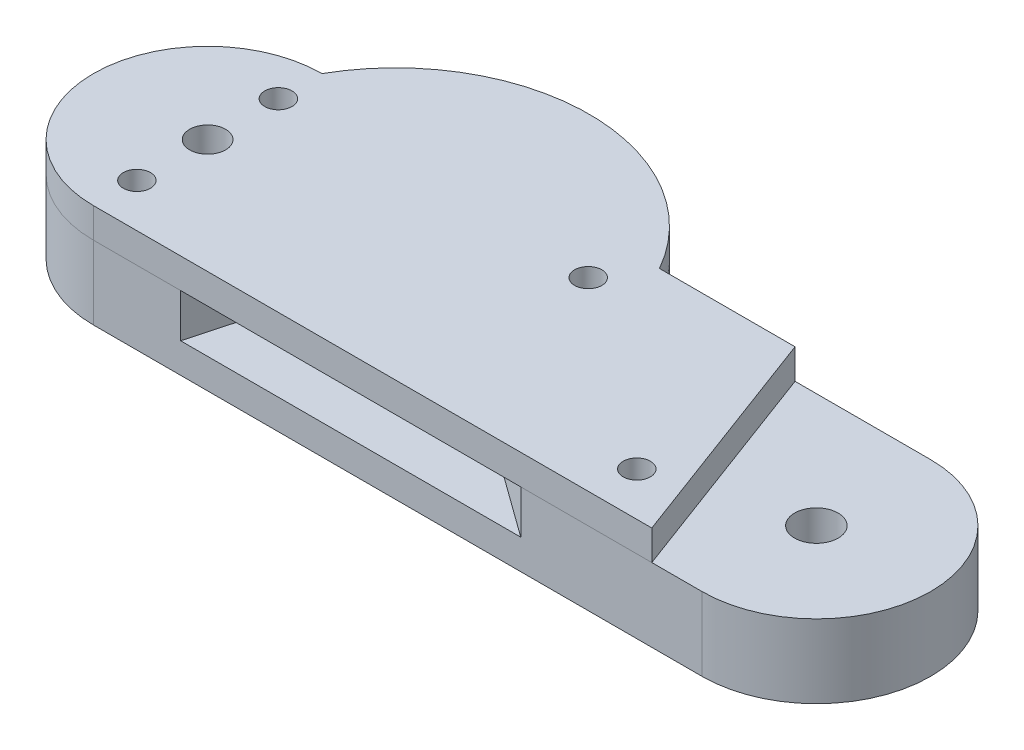
SolidWorks part; units mm, degrees
ref_plane "Front Plane" through (0, 0, 0) normal (0, 0, 1) x (1, 0, 0)
ref_plane "Top Plane" through (0, 0, 0) normal (0, 1, 0) x (1, 0, 0)
ref_plane "Right Plane" through (0, 0, 0) normal (1, 0, 0) x (0, 0, -1)
sketch "Sketch1" plane through (0, 0, 0) normal (0, 1, 0) x (1, 0, 0)
  line L0 (0, -10.5004) -> (-55.9305, -10.5004)
  line L1 (0, 10.5004) -> (-55.9305, 10.5004)
  line L5 (0, 11.5004) -> (-55.9305, 11.5004) construction
  line L6 (0, -11.5004) -> (-55.9305, -11.5004) construction
  circle A0 centre (0, 0) radius 2
  arc A1 (0, -10.5004) -> (0, 10.5004) centre (0, 0) ccw
  arc A2 (-55.9305, 10.5004) -> (-55.9305, -10.5004) centre (-55.9305, 0) ccw
  circle A3 centre (-55.9305, 0) radius 1.65
  arc A7 (0, -11.5004) -> (0, 11.5004) centre (0, 0) ccw construction
  arc A8 (-55.9305, 11.5004) -> (-55.9305, -11.5004) centre (-55.9305, 0) ccw construction
  arc A9 (-67.2423, -5.04) -> (-54.9145, -15.6487) centre (-55.7741, -4.1805) ccw construction
  arc A10 (-55.9305, 10.5004) -> (-55.9305, -10.5004) centre (-55.9305, 0) ccw construction
  dimension "D1" = 4
  dimension "D2" = 1
  dimension "D3" = 3.3
  dimension "D4" = 55.9305
extrude "Boss-Extrude1" add sketch "Sketch1" along normal mid plane 9.5
sketch "Sketch3" plane through (0, 0, 0) normal (0, 1, 0) x (1, 0, 0)
  line L0 (0, 0) -> (-47.1525, -15.3208) construction
  line L1 (0, 0) -> (24.7895, -42.9367) construction
  line L2 (0, 0) -> (-55.9305, 0) construction
  line L3 (24.7895, -42.9367) -> (-41.5934, 5.0595) construction
  line L4 (-41.5934, 5.0595) -> (-47.1525, -15.3208) construction
  line L5 (-41.5934, 5.0595) -> (-37.6461, 19.5308) construction
  line L6 (-41.5934, 5.0595) -> (-53.749, 13.8482) construction
  line L7 (22.8477, -44.0007) -> (-38.0092, 0) construction
  line L8 (-35.7518, 18.8753) -> (-39.2995, 5.869)
  line L9 (-43.8873, 4.25) -> (-54.8123, 12.149)
  line L11 (26.6452, -41.8104) -> (-39.2995, 5.869)
  line L12 (-39.6108, 19.9279) -> (-42.7627, 8.3729) construction
  line L13 (-42.7627, 8.3729) -> (-52.4686, 15.3905) construction
  line L14 (-40.9004, 0) -> (-45.9674, -18.5763) construction
  line L15 (-43.8873, 4.25) -> (-48.2065, -11.585)
  line L18 (-40.4216, 6.6802) -> (-50.8477, 14.2185) construction
  line L20 (-41.5934, 5.0595) -> (-52.0196, 12.5978) construction
  line L21 (-42.7652, 3.4387) -> (-53.1914, 10.977) construction
  line L23 (-43.5229, 5.5858) -> (-49.082, -14.7945) construction
  line L26 (-39.6639, 4.5332) -> (-45.223, -15.8471) construction
  line L27 (25.9613, -41.316) -> (-40.4216, 6.6802) construction
  line L28 (23.6177, -44.5574) -> (-42.7652, 3.4387) construction
  arc A1 (-48.2065, -11.585) -> (26.6452, -41.8104) centre (0, 0) ccw
  arc A4 (-55.9305, 10.5004) -> (-55.9305, -10.5004) centre (-55.9305, 0) ccw construction
  arc A7 (-35.7518, 18.8753) -> (-54.8123, 12.149) centre (-41.5934, 5.0595) ccw
  dimension "D1" = 99.1581
  dimension "D3" = 120
  dimension "D6" = 30
  dimension "D2" = 18
  dimension "D4" = 2
  dimension "D5" = 2
extrude "Cut-Extrude1" cut sketch "Sketch3" against normal mid plane 4
sketch "Sketch5" plane through (0, 0, 0) normal (0, 1, 0) x (1, 0, 0)
  line L0 (-40.4241, 1.7461) -> (-52.5322, 10.5004) construction
  line L1 (-40.4241, 1.7461) -> (-35.7382, 18.9254) construction
  line L2 (-52.5322, 10.5004) -> (-43.8873, 4.25) construction
  line L3 (-39.2995, 5.869) -> (-38.0362, 10.5004) construction
  line L4 (-55.9305, 10.5004) -> (-24.9177, 10.5004)
  line L5 (0, 10.5004) -> (-55.9305, 10.5004) construction
  circle A0 centre (-40.4241, 1.7461) radius 17.807
extrude "Boss-Extrude2" add sketch "Sketch5" along normal up to surface and the other way up to surface contours A0 region at (-40.4241, 0, -14.2141) up to face at (0, 4.75, 2) other way up to face at (-27.9653, -4.75, 0)
sketch "Sketch6" plane through (0, 0, 0) normal (0, 1, 0) x (1, 0, 0)
  line L0 (-39.2995, 5.869) -> (-16.6593, -10.5004)
  line L1 (-47.9107, -10.5004) -> (-43.8873, 4.25)
  line L2 (-43.8873, 4.25) -> (-54.8544, 12.1794)
  line L3 (-39.2995, 5.869) -> (-35.7382, 18.9254)
  line L4 (-16.6593, -10.5004) -> (-39.2995, 5.869) construction
  line L5 (-43.8873, 4.25) -> (-47.9107, -10.5004) construction
  line L6 (-52.5322, 10.5004) -> (-43.8873, 4.25) construction
  line L7 (-39.2995, 5.869) -> (-38.0362, 10.5004) construction
  line L8 (-55.9305, -10.5004) -> (0, -10.5004) construction
  line L9 (-16.6593, -10.5004) -> (-47.9107, -10.5004)
  arc A0 (-24.9177, 10.5004) -> (-55.9305, 10.5004) centre (-40.4241, 1.7461) ccw construction
  arc A1 (-35.7382, 18.9254) -> (-54.8544, 12.1794) centre (-40.4241, 1.7461) ccw
extrude "Cut-Extrude2" cut sketch "Sketch6" against normal mid plane 4
sketch "Sketch7" plane through (0, -4.75, 0) normal (0, -1, 0) x (1, 0, 0)
  line L0 (0, 0) -> (4.5965, 4.5965) construction
  line L1 (0, 0) -> (6.5004, 0) construction
  line L4 (0, 6.5004) -> (-55.9305, 6.5004)
  line L5 (-27.4616, -6.5004) -> (0, -6.5004)
  line L6 (0, 6.5004) -> (-55.9305, 6.5004) construction
  line L7 (-55.9305, -6.5004) -> (0, -6.5004) construction
  circle A3 centre (-27.4616, -6.5004) radius 1.25
  circle A4 centre (0, -6.5004) radius 1.25 construction
  circle A5 centre (4.5965, 4.5965) radius 1.25 construction
  arc A6 (0, -6.5004) -> (0, 6.5004) centre (0, 0) ccw
  arc A7 (-55.9305, 6.5004) -> (-53.5442, -6.0466) centre (-55.9305, 0) ccw
  arc A8 (-53.5442, -6.0466) -> (-27.4616, -6.5004) centre (-40.4241, -1.7461) ccw
  arc A9 (0, -6.5004) -> (0, 6.5004) centre (0, 0) ccw construction
  arc A10 (-55.9305, 6.5004) -> (-53.5442, -6.0466) centre (-55.9305, 0) ccw construction
  arc A11 (-53.5442, -6.0466) -> (-27.4616, -6.5004) centre (-40.4241, -1.7461) ccw construction
  circle A12 centre (-10, 6.5004) radius 1.25
  circle A13 centre (-55.9305, 6.5004) radius 1.25
  circle A14 centre (-55.9305, -6.5004) radius 1.25
  dimension "D4" = 2.5
  dimension "D2" = 10
  dimension "D3" = 45
  dimension "D1" = 4
extrude "Cut-Extrude3" cut sketch "Sketch7" against normal through all
sketch "Sketch8" plane through (0, -4.75, 0) normal (0, -1, 0) x (1, 0, 0)
  circle A0 centre (-55.9305, 6.5004) radius 2.75
  circle A1 centre (-55.9305, -6.5004) radius 2.75
  circle A2 centre (-27.4616, -6.5004) radius 2.75
  circle A3 centre (-10, 6.5004) radius 2.75
  dimension "D1" = 5.5
extrude "Cut-Extrude4" cut sketch "Sketch8" against normal blind 3.2
ref_plane "Plane1" through (0, 2, 0) normal (0, -1, 0) x (-1, 0, 0)
sketch "Sketch9" plane through (0, 4.75, 0) normal (0, 1, 0) x (1, 0, 0)
  line L0 (-12.4589, 10.5004) -> (-4.6195, -10.5004)
  line L1 (0, 10.5004) -> (-24.9177, 10.5004) construction
  line L2 (-55.9305, -10.5004) -> (0, -10.5004) construction
  line L3 (-6.5881, -5.2268) -> (-10, -6.5004) construction
  line L4 (-4.6195, -10.5004) -> (0, -10.5004)
  line L5 (-12.4589, 10.5004) -> (0, 10.5004)
  circle A0 centre (0, 0) radius 8 construction
  circle A1 centre (-10, -6.5004) radius 1.25 construction
  circle A2 centre (-10, -6.5004) radius 1.25 construction
  arc A3 (0, -10.5004) -> (0, 10.5004) centre (0, 0) ccw
  arc A4 (0, -10.5004) -> (0, 10.5004) centre (0, 0) ccw construction
  dimension "D1" = 16
extrude "Cut-Extrude5" cut sketch "Sketch9" against normal up to surface (2.75 mm away) up to face at (-39.9005, 2, -3.8681)
split "Split1" trim tools "Plane1" bodies to split 113 resulting bodies 111 112
